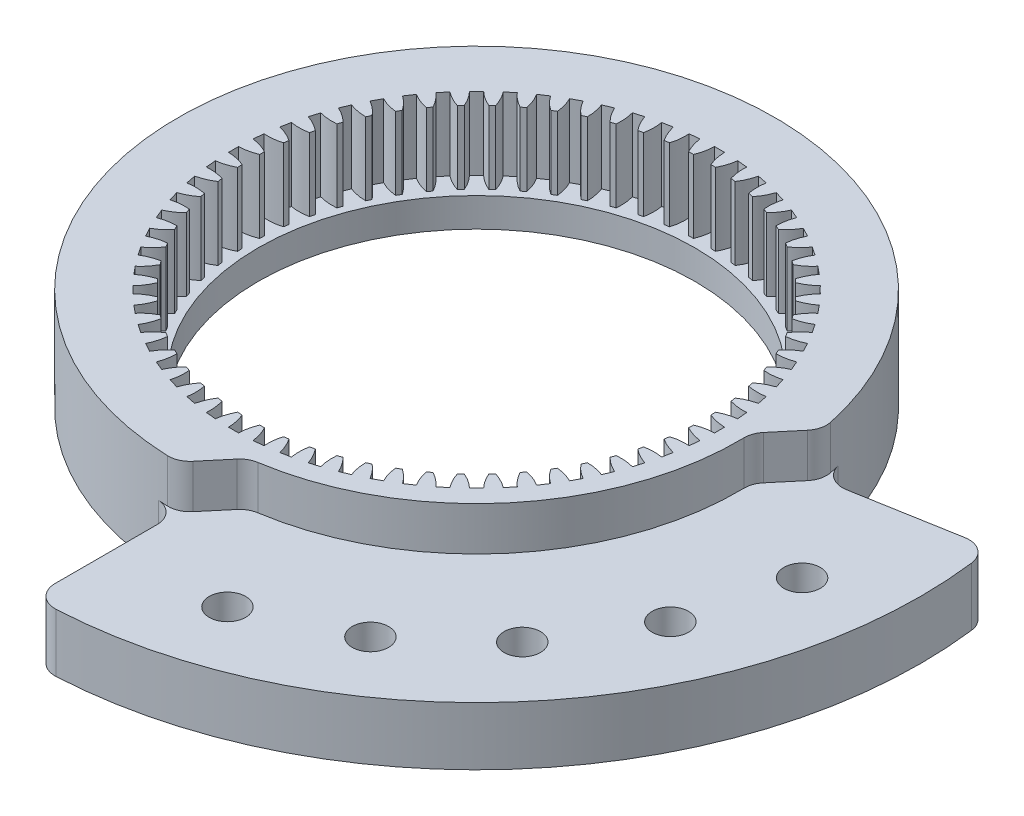
SolidWorks part; units mm, degrees
ref_plane "Front Plane" through (0, 0, 0) normal (0, 0, 1) x (1, 0, 0)
ref_plane "Top Plane" through (0, 0, 0) normal (0, 1, 0) x (1, 0, 0)
ref_plane "Right Plane" through (0, 0, 0) normal (1, 0, 0) x (0, 0, -1)
sketch "Sketch1" plane through (0, 0, 0) normal (0, 1, 0) x (1, 0, 0)
  circle A0 centre (0, 0) radius 16
  circle A1 centre (0, 0) radius 16.7
  circle A2 centre (0, 0) radius 15.5
  dimension "D1" = 32
  dimension "D2" = 33.4
  dimension "D3" = 1.2
extrude "Boss-Extrude1" add sketch "Sketch1" along normal mid plane 5 contours A1 A0 | A0 A2 | A2 region at (-15.5475, 0, 0) region at (-16.2277, 0, 0) region at (0, 0, 0)
sketch "Sketch7" plane through (0, 0, 0) normal (0, 1, 0) x (1, 0, 0)
  line L0 (16.7, 0) -> (-16.7, 0) construction
  line L1 (0, 16.7) -> (0, -16.7) construction
  circle A0 centre (0, 0) radius 16.7 construction
  point P7 (0, 0)
sketch "Sketch4" plane through (0, 0, 0) normal (0, 1, 0) x (1, 0, 0)
  line L0 (0, 0) -> (0, -30.5) construction
  line L10 (0, 0) -> (30.0366, 5.2963) construction
  line L11 (30.0366, 5.2963) -> (20.1886, 3.5598)
  line L12 (0, -30.5) -> (0, -20.5)
  circle A2 centre (0, 0) radius 15.5 construction
  circle A3 centre (0, 0) radius 15.5
  arc A4 (20.1886, 3.5598) -> (0, -20.5) centre (0, 0) ccw
  circle A9 centre (0, 0) radius 30.5 construction
  arc A10 (30.0366, 5.2963) -> (0, -30.5) centre (0, 0) cw
  dimension "D1" = 5
  dimension "D3" = 100
  dimension "D2" = 10
extrude "Boss-Extrude2" add sketch "Sketch4" along normal mid plane 5
sketch "Sketch3" plane through (0, 0, 0) normal (0, 1, 0) x (1, 0, 0)
  line L0 (0, 0) -> (0, 16.7) construction
  line L1 (-0.3927, 15.9952) -> (0.3927, 15.9952) construction
  line L2 (-0.3434, 15.4962) -> (0, 0) construction
  line L3 (0, 13.7683) -> (-0.5155, 16.692) construction
  line L4 (0, 0) -> (0.8194, 16.6799) construction
  line L5 (0.3927, 15.9952) -> (1.177, 15.9566) construction
  line L6 (0, 15.5) -> (0, 16.7) construction
  line L7 (0.3434, 15.4962) -> (0.3434, 16.7) construction
  line L8 (0.3434, 16.0981) -> (-0.3121, 16.0981) construction
  arc A1 (-0.5957, 16.6894) -> (-0.3434, 15.4962) centre (-3.6364, 15.4232) cw construction
  arc A2 (0.5957, 16.6894) -> (0.3434, 15.4962) centre (3.6364, 15.4232) ccw construction
  circle A3 centre (0, 0) radius 15.5 construction
  arc A4 (0.3434, 15.4962) -> (-0.3434, 15.4962) centre (0, 0) ccw construction
  circle A5 centre (0, 0) radius 16 construction
  circle A6 centre (0, 0) radius 16.7 construction
  arc A7 (0.5957, 15.5068) -> (-0.5957, 15.5068) centre (0, 32.1962) cw
  arc A8 (0.5957, 16.6894) -> (-0.5957, 16.6894) centre (0, 0) ccw construction
  arc A9 (-0.5957, 15.5068) -> (-0.3434, 16.7) centre (-3.6364, 16.773) ccw
  arc A10 (0.5957, 15.5068) -> (0.3434, 16.7) centre (3.6364, 16.773) cw
  arc A11 (0.3434, 16.7) -> (-0.3434, 16.7) centre (0, 32.1962) cw
  dimension "D3" = 2.813
  dimension "D2" = 10
extrude "Cut-Extrude1" cut sketch "Sketch3" against normal through all both and the other way through all
pattern_circular "CirPattern1" count 64 over 360 about axis through (0, 2.5, 0) along (0, 1, 0) of "Cut-Extrude1"
sketch "Sketch5" plane through (0, 0, 0) normal (0, 1, 0) x (1, 0, 0)
  circle A0 centre (0, 0) radius 15.5183
extrude "Cut-Extrude2" cut sketch "Sketch5" against normal through all both and the other way through all
sketch "Sketch8" plane through (0, -2.5, 0) normal (0, -1, 0) x (1, 0, 0)
  line L2 (0, 30.5) -> (0, 20.5)
  line L6 (0, 30.5) -> (0, 20.5)
  line L8 (20.1886, -3.5598) -> (30.0366, -5.2963)
  line L9 (20.1886, -3.5598) -> (30.0366, -5.2963)
  circle A0 centre (0, 0) radius 15
  arc A3 (30.0366, -5.2963) -> (0, 30.5) centre (0, 0) ccw
  arc A4 (30.0366, -5.2963) -> (0, 30.5) centre (0, 0) ccw
  arc A5 (0, 20.5) -> (20.1886, -3.5598) centre (0, 0) ccw
  arc A7 (0, 20.5) -> (20.1886, -3.5598) centre (0, 0) ccw
  dimension "D2" = 30
  dimension "D1" = 0
extrude "Boss-Extrude3" add sketch "Sketch8" along normal blind 2
sketch "Sketch6" plane through (0, 2.5, 0) normal (0, 1, 0) x (1, 0, 0)
  line L0 (0, 0) -> (7.3135, -24.4287) construction
  line L2 (0, -16.7) -> (0, 16.7) construction
  line L4 (0, -20.5) -> (0, -30.5) construction
  circle A3 centre (7.3135, -24.4287) radius 0.5
  point P5 (0, -25.5)
  point P11 (0, 0)
  dimension "D2" = 16.667
  dimension "D1" = 1
  dimension "D3" = 25.5
extrude "Cut-Extrude3" cut sketch "Sketch6" against normal through all
pattern_circular "CirPattern2" count 5 over 66.667 about axis through (0, -2.5, 0) along (0, -1, 0) of "Cut-Extrude3" reverse direction yes
sketch "Sketch9" plane through (0, 2.5, 0) normal (0, 1, 0) x (1, 0, 0)
  line L0 (20.1886, 3.5598) -> (17.9763, 0.9233)
  line L1 (0, -20.5) -> (2.2123, -17.8635)
  line L2 (0, 0) -> (16.4873, -13.8345) construction
  line L3 (2.2123, -17.8635) -> (17.9763, 0.9233) construction
  line L4 (20.1886, 3.5598) -> (30.0366, 5.2963)
  line L5 (0, -20.5) -> (0, -30.5)
  line L6 (0, 0) -> (135.2451, 0) construction
  line L7 (30.0366, 5.2963) -> (20.1886, 3.5598) construction
  arc A0 (2.2123, -17.8635) -> (17.9763, 0.9233) centre (0, 0) ccw
  arc A1 (0, -30.5) -> (30.0366, 5.2963) centre (0, 0) ccw construction
  arc A2 (0, -30.5) -> (30.0366, 5.2963) centre (0, 0) ccw
  point P5 (10.0943, -8.4701)
  point P8 (20.1886, 3.5598)
  point P17 (0, 0)
  point P18 (21.6932, 3.8251)
  dimension "D1" = 36
extrude "Cut-Extrude4" cut sketch "Sketch9" against normal offset from surface (3 mm away) 4 up to face at (14.1559, -4.5, 21.7839)
fillet "Fillet1" radius 1.5 6 edges at (20.1886, -2.5, -3.5598) (30.0366, -2.5, -5.2963) (0, -2.5, 30.5) (0, -2.5, 20.5) (17.9763, 1, -0.9233) (2.2123, 1, 17.8635)
fillet "Fillet2" radius 1.5 2 edges at (0, 1, 20.5) (20.1886, 1, -3.5598)
hole_wizard "Ø2.5mm Dowel Hole1" positions "Sketch12" profile "Sketch11" hole size "Ø2.5" standard "ISO"
sketch "Sketch12" plane through (0, -4.5, 0) normal (0, -1, 0) x (-1, 0, 0)
  point P0 (-7.3135, -24.4287)
  point P3 (-14.0125, -21.3049)
  point P6 (-19.5341, -16.3911)
  point P9 (-23.4145, -10.1)
  point P16 (-25.3276, -2.9604)
sketch "Sketch11" plane through (7.3135, -4.5, 24.4287) normal (1, 0, 0) x (0, 0, -1)
  line L0 (0, 0) -> (0, 4.7511)
  line L1 (0, 4.7511) -> (1.25, 4)
  line L2 (1.25, 4) -> (1.25, 0)
  line L5 (1.25, 0) -> (0, 0)
  line L10 (0, 4.7511) -> (-1.25, 4) construction
  line L11 (0, -6.35) -> (0, 107.95) construction
  dimension "Hole Dia." = 2.5
  dimension "Hole Depth" = 4
  dimension "Drill Angle" = 118
ref_axis "Axis2" through (0, -4.5, 0) along (0, 1, 0)
equation "\"Module\"= .5"
equation "\"Number of Teeth\"=64"
equation "\"D1@Sketch1\"=\"Module\"* \"Number of Teeth\""
equation "\"D2@Sketch1\"=(\"Number of Teeth\" + 2) * \"Module\" + .4"
equation "\"D3@Sketch1\"=\"Module\" * if( \"Module\" => 1.25, 2.25, 2.4)"
equation "\"D3@Sketch3\"=180 / \"Number of Teeth\""
equation "\"D1@CirPattern1\"=\"Number of Teeth\""
